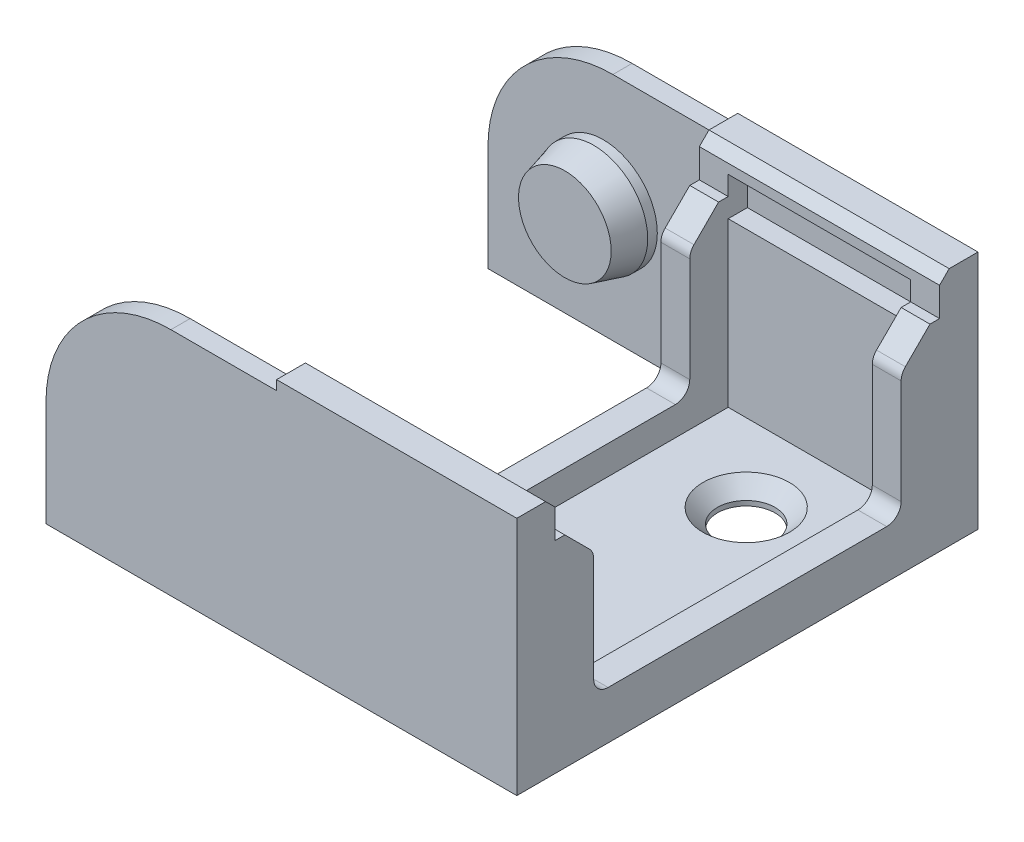
SolidWorks part; units mm, degrees
ref_plane "Front" through (0, 0, 0) normal (0, 0, 1) x (1, 0, 0)
ref_plane "Top" through (0, 0, 0) normal (0, 1, 0) x (1, 0, 0)
ref_plane "Right" through (0, 0, 0) normal (1, 0, 0) x (0, 0, -1)
sketch "Эскиз1" plane through (0, 0, 0) normal (0, 0, 1) x (1, 0, 0)
  line L1 (-38.7795, 23.7195) -> (-13.7795, 23.7195)
  line L2 (-38.7795, 23.7195) -> (-38.7795, -1.2805)
  line L3 (-38.7795, -1.2805) -> (-13.7795, -1.2805)
  line L4 (-13.7795, 23.7195) -> (-13.7795, -1.2805)
  dimension "D1" = 25
  dimension "D2" = 25
extrude "Бобышка-Вытянуть1" add sketch "Эскиз1" along normal blind 4
sketch "Эскиз2" plane through (0, 0, 0) normal (0, 0, -1) x (-1, 0, 0)
  line L0 (38.7795, 22.7195) -> (62.7795, 22.7195)
  line L1 (38.7795, 23.7195) -> (38.7795, -1.2805) construction
  line L3 (62.7795, 22.7195) -> (62.7795, -1.2805)
  line L4 (62.7795, -1.2805) -> (38.7795, -1.2805)
  line L5 (38.7795, -1.2805) -> (38.7795, 22.7195)
  dimension "D1" = 24
  dimension "D2" = 24
extrude "Бобышка-Вытянуть2" add sketch "Эскиз2" against normal blind 2
sketch "Эскиз3" plane through (0, 0, 2) normal (0, 0, 1) x (1, 0, 0)
  line L1 (-38.7795, -1.2805) -> (-62.7795, -1.2805) construction
  line L2 (-62.7795, -1.2805) -> (-62.7795, 22.7195) construction
  circle A0 centre (-50.7795, 10.7195) radius 5.625
  dimension "D2" = 11.25
  dimension "D1" = 12
  dimension "D3" = 12
extrude "Бобышка-Вытянуть3" add sketch "Эскиз3" along normal blind 4
chamfer "Фаска1" distance 3 angle 15 1 edges at (-45.1545, 10.7195, 6) first distance on face at (-45.1545, 10.7195, 6)
sketch "Эскиз4" plane through (0, 0, 6) normal (0, 0, 1) x (1, 0, 0)
  circle A1 centre (-50.7795, 10.7195) radius 13
  circle A4 centre (-50.7795, 10.7195) radius 7.5542
sketch "Эскиз5" plane through (0, 0, 4) normal (0, 0, 1) x (1, 0, 0)
  line L0 (-18.982, 10.7195) -> (-0.7795, 10.7195) construction
  line L1 (-18.982, 22.7195) -> (-0.7795, 22.7195)
  line L2 (-18.982, -1.2805) -> (-0.7795, -1.2805)
  line L3 (-13.7795, -1.2805) -> (-13.7795, 23.7195) construction
  line L4 (-38.7795, -1.2805) -> (-13.7795, -1.2805) construction
  arc A0 (-18.982, 22.7195) -> (-18.982, -1.2805) centre (-18.982, 10.7195) ccw
  arc A1 (-0.7795, -1.2805) -> (-0.7795, 22.7195) centre (-0.7795, 10.7195) ccw
  point P2 (-9.8808, 10.7195)
  dimension "D1" = 13
  dimension "D2" = 12
  dimension "D3" = 12
extrude "Бобышка-Вытянуть4" add sketch "Эскиз5" against normal blind 2
sketch "Эскиз6" plane through (0, 0, 2) normal (0, 0, -1) x (-1, 0, 0)
  circle A0 centre (0.7795, 10.7195) radius 5
  arc A1 (0.7795, 22.7195) -> (0.7795, -1.2805) centre (0.7795, 10.7195) ccw construction
extrude "Вырез-Вытянуть2" cut sketch "Эскиз6" against normal blind 10
sketch "Эскиз8" plane through (0, 0, 4) normal (0, 0, 1) x (1, 0, 0)
  line L5 (-38.7795, 3.7195) -> (-35.7795, 3.7195)
  line L6 (-38.7795, -1.2805) -> (-13.7795, -1.2805)
  line L7 (-38.7795, -1.2805) -> (-38.7795, 3.7195)
  line L9 (-13.7795, -1.2805) -> (-13.7795, 3.7195)
  line L10 (-35.7795, 3.7195) -> (-35.7795, 0.7195)
  line L11 (-35.7795, 0.7195) -> (-16.7795, 0.7195)
  line L12 (-16.7795, 0.7195) -> (-16.7795, 3.7195)
  line L13 (-16.7795, 3.7195) -> (-13.7795, 3.7195)
  line L14 (-13.7795, 22.7195) -> (-13.7795, 23.7195) construction
  dimension "D1" = 3
  dimension "D2" = 3
  dimension "D3" = 2
  dimension "D4" = 5
  dimension "D5" = 5
extrude "Бобышка-Вытянуть6" add sketch "Эскиз8" along normal blind 20
sketch "Эскиз9" plane through (0, 0, 4) normal (0, 0, 1) x (1, 0, 0)
  line L0 (-38.7795, 23.7195) -> (-38.7795, 3.7195) construction
  line L1 (-35.7795, 20.7195) -> (-16.7795, 20.7195)
  line L2 (-35.7795, 20.7195) -> (-35.7795, 17.7195)
  line L3 (-35.7795, 17.7195) -> (-16.7795, 17.7195)
  line L4 (-16.7795, 20.7195) -> (-16.7795, 17.7195)
  line L5 (-13.7795, 22.7195) -> (-13.7795, 23.7195) construction
  line L6 (-13.7795, 23.7195) -> (-38.7795, 23.7195) construction
  dimension "D1" = 3
  dimension "D2" = 3
  dimension "D3" = 3
  dimension "D4" = 6
extrude "Вырез-Вытянуть4" cut sketch "Эскиз9" against normal blind 2
chamfer "Фаска2" distance 1 angle 45 1 edges at (-26.2795, 20.7195, 4)
chamfer "Фаска3" distance 1 angle 75 1 edges at (-5.7795, 10.7195, 2) first distance on face at (-5.7795, 10.7195, 2)
fillet "Скругление1" radius 13 1 edges at (-62.7795, 22.7195, 1)
chamfer "Фаска4" distance 1 angle 45 1 edges at (-26.2795, 23.7195, 4)
sketch "Эскиз11" plane through (0, 3.7195, 0) normal (0, 1, 0) x (1, 0, 0)
  line L0 (-35.7795, -24) -> (-35.7795, -4) construction
  line L1 (-38.7795, -4) -> (-35.7795, -4)
  line L2 (-38.7795, -4) -> (-38.7795, -8)
  line L3 (-38.7795, -8) -> (-35.7795, -8)
  line L4 (-35.7795, -4) -> (-35.7795, -8)
  dimension "D1" = 4
extrude "Бобышка-Вытянуть7" add sketch "Эскиз11" along normal blind 16
pattern_linear "Линейный массив1" count 2 spacing 22 along (1, 0, 0) of "Бобышка-Вытянуть7"
chamfer "Фаска6" distance 3 angle 45 2 edges at (-15.2795, 19.7195, 8) (-37.2795, 19.7195, 8)
fillet "Скругление2" radius 1.5 4 edges at (-15.2795, 3.7195, 8) (-15.2795, 16.7195, 8) (-37.2795, 16.7195, 8) (-37.2795, 3.7195, 8)
sketch "Эскиз13" plane through (0, 0, 4) normal (0, 0, 1) x (1, 0, 0)
  line L1 (-13.7795, 22.7195) -> (26.5136, 22.7195)
  line L2 (-13.7795, 22.7195) -> (-13.7795, -4.872)
  line L3 (-13.7795, -4.872) -> (26.5136, -4.872)
  line L4 (26.5136, 22.7195) -> (26.5136, -4.872)
extrude "Вырез-Вытянуть6" cut sketch "Эскиз13" against normal blind 100
sketch "Эскиз14" plane through (0, 0.7195, 0) normal (0, 1, 0) x (1, 0, 0)
  circle A0 centre (-25.8243, -12.0797) radius 3
extrude "Вырез-Вытянуть7" cut sketch "Эскиз14" against normal blind 100
chamfer "Фаска7" distance 1.5 angle 45 1 edges at (-25.8243, 0.7195, 15.0797)
mirror "Зеркальное отражение1" about plane through (0, 0, 24) normal (0, 0, -1) of bodies 116 109
